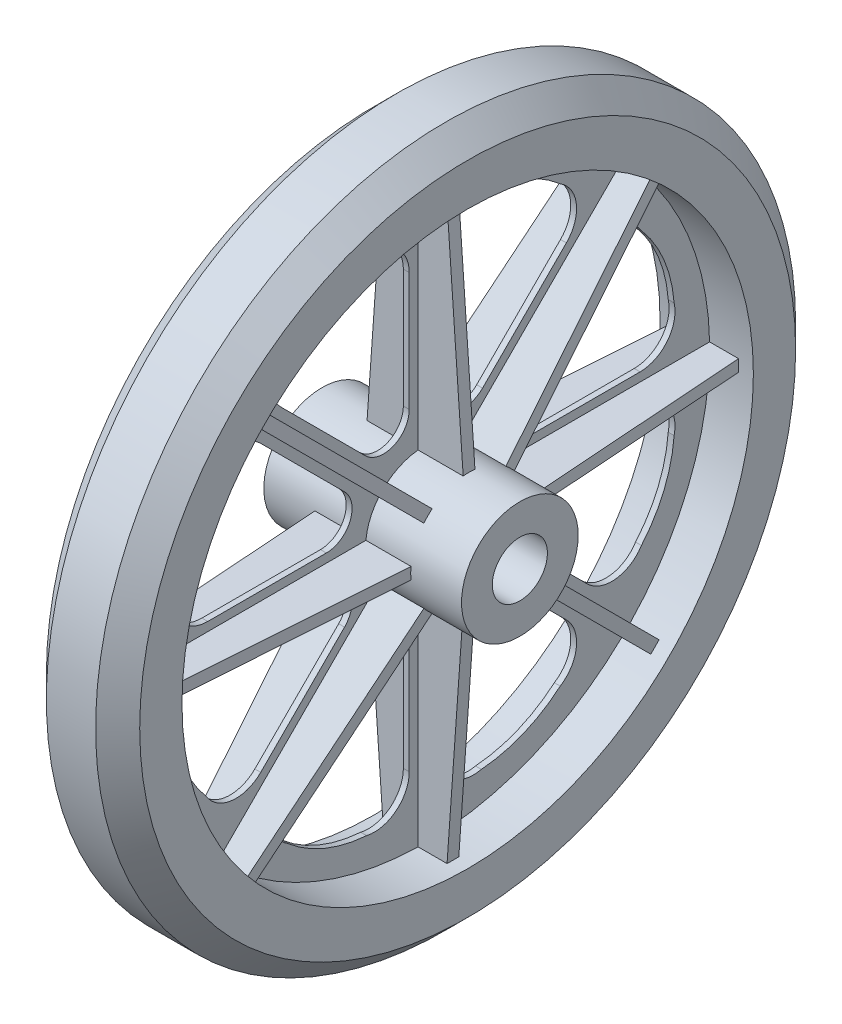
SolidWorks part; units mm, degrees
ref_plane "Plano frontal" through (0, 0, 0) normal (0, 0, 1) x (1, 0, 0)
ref_plane "Plano superior" through (0, 0, 0) normal (0, 1, 0) x (1, 0, 0)
ref_plane "Plano direito" through (0, 0, 0) normal (1, 0, 0) x (0, 0, -1)
sketch "Esboço1" plane through (0, 0, 0) normal (1, 0, 0) x (0, 0, -1)
  circle A0 centre (0, 0) radius 15.875
  dimension "D1" = 31.75
extrude "Ressalto-extrusão1" add sketch "Esboço1" along normal blind 26.9 and the other way blind 26.9
sketch "Esboço2" plane through (0, 0, 0) normal (1, 0, 0) x (0, 0, -1)
  circle A0 centre (0, 0) radius 95.25
  dimension "D1" = 190.5
extrude "Ressalto-extrusão2" add sketch "Esboço2" along normal blind 0.8 and the other way blind 0.8
sketch "Esboço3" plane through (0, 0, 0) normal (1, 0, 0) x (0, 0, -1)
  circle A0 centre (0, 0) radius 95.25 construction
  circle A1 centre (0, 0) radius 95.25
  circle A2 centre (0, 0) radius 77.75
  dimension "D1" = 17.5
extrude "Ressalto-extrusão3" add sketch "Esboço3" along normal blind 12.7 and the other way blind 12.7
sketch "Esboço6" plane through (0.8, 0, 0) normal (1, 0, 0) x (0, 0, -1)
  line L0 (0, 0) -> (0, 95.25) construction
  line L1 (0, 0) -> (67.3519, 67.3519) construction
  line L2 (4, 58.8207) -> (4, 26.5563)
  line L3 (15.9497, 21.6066) -> (38.7641, 44.4209)
  circle A0 centre (0, 0) radius 95.25 construction
  circle A1 centre (0, 0) radius 95.25 construction
  arc A3 (4, 26.5563) -> (15.9497, 21.6066) centre (11, 26.5563) ccw
  arc A4 (38.7641, 44.4209) -> (37.0912, 59.1884) centre (32.0466, 51.1384) ccw
  arc A5 (4, 58.8207) -> (15.6251, 68.0799) centre (13.5, 58.8207) cw
  arc A6 (15.6251, 68.0799) -> (37.0912, 59.1884) centre (12.8815, 31.0988) cw
  dimension "D3" = 4
  dimension "D5" = 9.5
  dimension "D6" = 9.5
  dimension "D7" = 7
  dimension "D2" = 45
  dimension "D4" = 4
extrude "Corte-extrusão1" cut sketch "Esboço6" against normal through all
ref_plane "Plano1" through (0, 88.8284, 0) normal (0, 1, 0) x (1, 0, 0)
sketch "Esboço7" plane through (0, 0, 0) normal (0, 1, 0) x (1, 0, 0)
  line L0 (26.9, -15.875) -> (26.9, 15.875) construction
  line L1 (-14.2, -1.6) -> (14.2, -1.6)
  line L2 (-14.2, -1.6) -> (-14.2, 1.6)
  line L3 (-14.2, 1.6) -> (14.2, 1.6)
  line L4 (14.2, -1.6) -> (14.2, 1.6)
  line L5 (-14.2, -1.6) -> (14.2, 1.6) construction
  line L6 (-14.2, 1.6) -> (14.2, -1.6) construction
  point P0 (0, 0)
  dimension "D1" = 12.7
  dimension "D2" = 3.2
sketch "Esboço8" plane through (0, 88.8284, 0) normal (0, 1, 0) x (1, 0, 0)
  line L1 (-7.9, -1.6) -> (7.9, -1.6)
  line L2 (-7.9, -1.6) -> (-7.9, 1.6)
  line L3 (-7.9, 1.6) -> (7.9, 1.6)
  line L4 (7.9, -1.6) -> (7.9, 1.6)
  line L5 (-7.9, -1.6) -> (7.9, 1.6) construction
  line L6 (-7.9, 1.6) -> (7.9, -1.6) construction
  point P0 (0, 0)
  dimension "D1" = 15.8
  dimension "D2" = 3.2
loft "Loft2" add profiles "Esboço7", "Esboço8"
pattern_circular "PadrãoCircular2" count 8 over 360 about axis through (-12.7, 0, 0) along (1, 0, 0) of "Loft2", "Corte-extrusão1"
sketch "Esboço9" plane through (-26.9, 0, 0) normal (-1, 0, 0) x (0, 0, 1)
  circle A0 centre (0, 0) radius 7.5
extrude "Corte-extrusão2" cut sketch "Esboço9" against normal through all
chamfer "Chanfro1" distance 6 angle 45 2 edges at (12.7, 0, -95.25) (-12.7, 0, -95.25)
